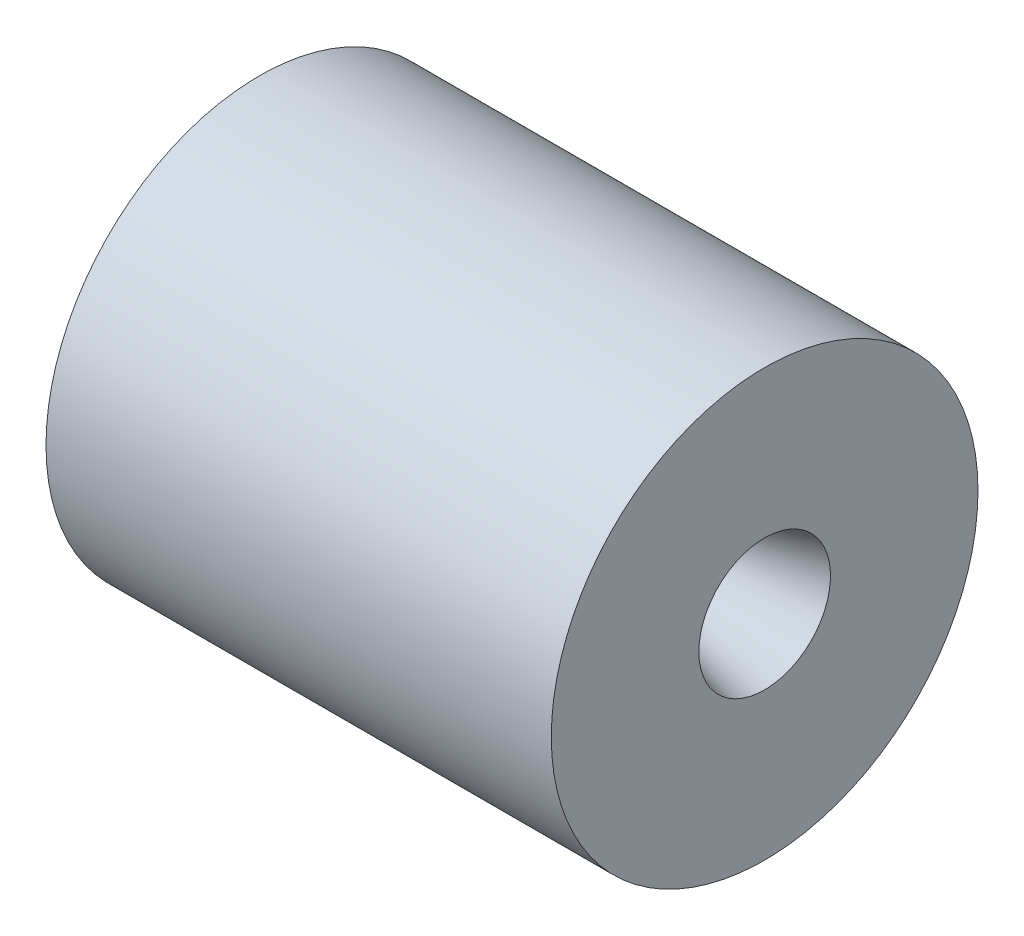
SolidWorks part; units mm, degrees
material "AISI 304"
ref_plane "Front Plane" through (0, 0, 0) normal (0, 0, 1) x (1, 0, 0)
ref_plane "Top Plane" through (0, 0, 0) normal (0, 1, 0) x (1, 0, 0)
ref_plane "Right Plane" through (0, 0, 0) normal (1, 0, 0) x (0, 0, -1)
sketch "chamberNozzle" plane through (0, 0, 0) normal (0, 0, 1) x (1, 0, 0)
  line L0 (0, 0) -> (366.3783, 0) construction
  line L1 (0, 0) -> (0, 38.1) construction
  line L2 (0, 38.1) -> (110.897, 38.1)
  line L3 (158.9188, 24.511) -> (158.9188, 13.97) construction
  line L4 (117.247, 36.3985) -> (153.6483, 15.3822)
  line L5 (150.9294, 13.97) -> (106.9103, 13.97) construction
  line L6 (161.647, 14.3292) -> (210.5452, 27.4314)
  line L7 (210.5452, 27.4314) -> (210.5452, 0) construction
  line L13 (160.3322, 19.2361) -> (209.2304, 32.3383) construction
  line L17 (0, 43.18) -> (110.897, 43.18) construction
  line L18 (119.787, 40.7979) -> (156.1883, 19.7816) construction
  line L19 (0, 38.1) -> (0, 45.72)
  line L20 (0, 88.9) -> (210.5452, 88.9)
  line L21 (210.5452, 88.9) -> (210.5452, 27.4314)
  line L22 (0, 45.72) -> (5.08, 45.72)
  line L23 (5.08, 45.72) -> (5.08, 55.88)
  line L24 (5.08, 55.88) -> (0, 55.88)
  line L25 (0, 55.88) -> (0, 88.9)
  arc A0 (153.6483, 15.3822) -> (161.647, 14.3292) centre (158.9188, 24.511) ccw
  arc A1 (110.897, 38.1) -> (117.247, 36.3985) centre (110.897, 25.4) cw
  arc A3 (156.1883, 19.7816) -> (160.3322, 19.2361) centre (158.9188, 24.511) ccw
  arc A4 (110.897, 43.18) -> (119.787, 40.7979) centre (110.897, 25.4) cw construction
  point P16 (114.3, 38.1)
  point P29 (5.08, 50.8)
  dimension "D4" = 21.082
  dimension "D9" = 12.7
  dimension "D1" = 38.1
  dimension "D5" = 30
  dimension "D6" = 15
  dimension "D11" = 50.8
  dimension "D12" = 10.16
  dimension "D13" = 12.7
  dimension "D14" = 5.08
  dimension "D10" = 5.08
revolve "Revolve1" add sketch "chamberNozzle" angle 360 about L0 region at (113.2306, 59.3604, 0)
sketch "Sketch3" plane through (0, 0, 0) normal (-1, 0, 0) x (0, 0, 1)
  circle A0 centre (0, 0) radius 69.85 construction
  circle A1 centre (-69.85, 0) radius 6.35
  circle A2 centre (-21.5848, 66.4313) radius 6.35
  circle A3 centre (56.5098, 41.0568) radius 6.35
  circle A4 centre (56.5098, -41.0568) radius 6.35
  circle A5 centre (-21.5848, -66.4313) radius 6.35
  point P15 (0, 0)
  dimension "D1" = 139.7
  dimension "D2" = 12.7
  dimension "D3" = 5
extrude "Cut-Extrude2" cut sketch "Sketch3" against normal blind 25.4
equation "\"l_star\"= .8m'characteristic length"
equation "\"R_t\"= .55in'throat radius"
equation "\"V_c\"= \"l_star\" * \"R_t\"'chamber volume"
equation "\"D_c\"= 3in'chamber diameter"
equation "\"L_c\"= \"V_c\" / ( ( pi * \"D_c\" ) / 4 )'chamber length"
equation "\"eps_x\"= 3.8557'expansion ratio"
equation "\"D_e\"= \"R_t\" * 2 * sqr ( \"eps_x\" )'exit diameter"
equation "\"arc_t\"= 1.5in * \"R_t\"'arc between convergent and divergent"
equation "\"D3@chamberNozzle\" = \"R_t\""
equation "\"D7@chamberNozzle\" = \"D_e\" / 2"
equation "\"D1@chamberNozzle\" = \"D_c\" / 2"
equation "\"D13@chamberNozzle\" = \"D11@chamberNozzle\" / 4"
equation "\"D14@chamberNozzle\" = \"D12@chamberNozzle\" / 2"
